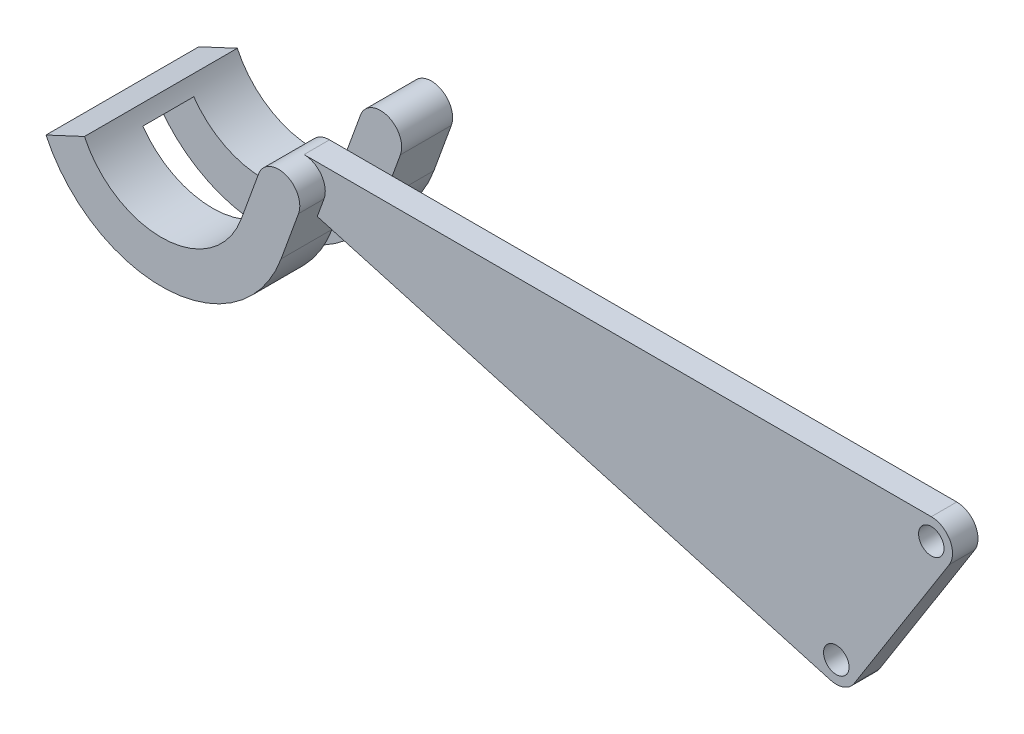
SolidWorks part; units mm, degrees
ref_plane "前基準面" through (0, 0, 0) normal (0, 0, 1) x (1, 0, 0)
ref_plane "上基準面" through (0, 0, 0) normal (0, 1, 0) x (1, 0, 0)
ref_plane "右基準面" through (0, 0, 0) normal (1, 0, 0) x (0, 0, -1)
sketch "草圖1" plane through (0, 0, 0) normal (0, 0, 1) x (1, 0, 0)
  line L0 (0, 0) -> (36.94, 0) construction
  line L1 (36.94, 0) -> (31.3447, -8.8495) construction
  line L2 (31.3447, -8.8495) -> (0, 0) construction
  line L3 (0, 1.25) -> (36.94, 1.25)
  line L4 (-0.3396, -1.203) -> (31.0051, -10.0525)
  line L5 (36.94, 0) -> (37.9965, -0.668) construction
  line L6 (37.9965, -0.668) -> (32.4012, -9.5175)
  arc A0 (0, 1.25) -> (-0.3396, -1.203) centre (0, 0) ccw
  arc A1 (37.9965, -0.668) -> (36.94, 1.25) centre (36.94, 0) ccw
  arc A2 (31.0051, -10.0525) -> (32.4012, -9.5175) centre (31.3447, -8.8495) ccw
  circle A3 centre (0, 0) radius 0.75
  circle A4 centre (36.94, 0) radius 0.75
  circle A5 centre (31.3447, -8.8495) radius 0.75
  dimension "D1" = 2.5
  dimension "D5" = 1.5
  dimension "D6" = 2.5
  dimension "D2" = 32.57
  dimension "D3" = 36.94
  dimension "D4" = 10.47
extrude "填料-伸長1" add sketch "草圖1" along normal mid plane 1.5 contours L3 A1 L6 A2 L4 A0
sketch "草圖2" plane through (0, 0, 0.75) normal (0, 0, 1) x (1, 0, 0)
  circle A0 centre (31.3447, -8.8495) radius 0.75 construction
  circle A1 centre (36.94, 0) radius 0.75 construction
  circle A2 centre (0, 0) radius 0.75 construction
  circle A3 centre (31.3447, -8.8495) radius 0.75
  circle A4 centre (36.94, 0) radius 0.75
  circle A5 centre (0, 0) radius 0.75
extrude "除料-伸長1" cut sketch "草圖2" against normal blind 11.5
sketch "草圖3" plane through (0, 0, -0.75) normal (0, 0, -1) x (-1, 0, 0)
  line L0 (1.1746, 0.4275) -> (2.2007, -2.3916)
  line L1 (2.2007, -2.3916) -> (-0.1486, -3.2466)
  line L2 (-0.1486, -3.2466) -> (-1.1746, -0.4275)
  line L3 (11.4307, -2.7945) -> (13.6964, -3.8511)
  line L4 (0, 1.25) -> (-36.94, 1.25) construction
  line L5 (11.4307, -2.7945) -> (15.8357, 6.6521) construction
  arc A2 (1.1746, 0.4275) -> (-1.1746, -0.4275) centre (0, 0) ccw
  arc A3 (2.2007, -2.3916) -> (11.4307, -2.7945) centre (6.8991, -0.6815) ccw
  arc A4 (-0.1486, -3.2466) -> (13.6964, -3.8511) centre (6.8991, -0.6815) ccw
  arc A5 (0.3396, -1.203) -> (0, 1.25) centre (0, 0) ccw construction
  point P12 (14.5062, 6.7347)
  point P18 (13.7884, 6.4837)
  circle M7 centre (0, 0) radius 0.75
  arc M9 (0.3396, -1.203) -> (0, 1.25) centre (0, 0) ccw
  line M14 (-31.0051, -10.0525) -> (0.3396, -1.203)
  dimension "D4" = 5
  dimension "D1" = 70
  dimension "D2" = 135
  dimension "D3" = 3
extrude "填料-伸長2" add sketch "草圖3" against normal blind 3 and the other way blind 6 contours M7 | A2 L2 M9 M14 M7 | L2 L1 L0 M9 M14 | L1 A4 L3 A3 region at (-1.0794, -0.5528, -0.75) region at (-0.7507, -1.8908, -0.75) region at (-6.6745, -5.8266, -0.75) region at (0, 0, -0.75)
sketch "草圖4" plane through (0, 0, -0.75) normal (0, 0, -1) x (-1, 0, 0)
  line L1 (-0.1486, -3.2466) -> (-1.1746, -0.4275) construction
  line L2 (1.1746, 0.4275) -> (2.2007, -2.3916) construction
  line L3 (11.4307, -2.7945) -> (13.6964, -3.8511) construction
  line L4 (-0.1486, -3.2466) -> (-1.1746, -0.4275)
  line L5 (1.1746, 0.4275) -> (2.2007, -2.3916)
  line L6 (10.9949, -3.5493) -> (13.0428, -4.9833)
  line L7 (10.9949, -3.5493) -> (18.6679, 7.4088) construction
  arc A0 (2.2007, -2.3916) -> (11.4307, -2.7945) centre (6.8991, -0.6815) ccw construction
  arc A1 (-0.1486, -3.2466) -> (13.6964, -3.8511) centre (6.8991, -0.6815) ccw construction
  arc A2 (1.1746, 0.4275) -> (-1.1746, -0.4275) centre (0, 0) ccw construction
  arc A3 (2.2007, -2.3916) -> (10.9949, -3.5493) centre (6.8991, -0.6815) ccw
  arc A4 (-0.1486, -3.2466) -> (13.0428, -4.9833) centre (6.8991, -0.6815) ccw
  arc A5 (1.1746, 0.4275) -> (-1.1746, -0.4275) centre (0, 0) ccw
  point P10 (12.9675, 2.3575)
  point P11 (13.1916, 3.2267)
  point P13 (13.203, 4.4613)
  dimension "D1" = 10
extrude "除料-伸長2" cut sketch "草圖4" along normal blind 3
